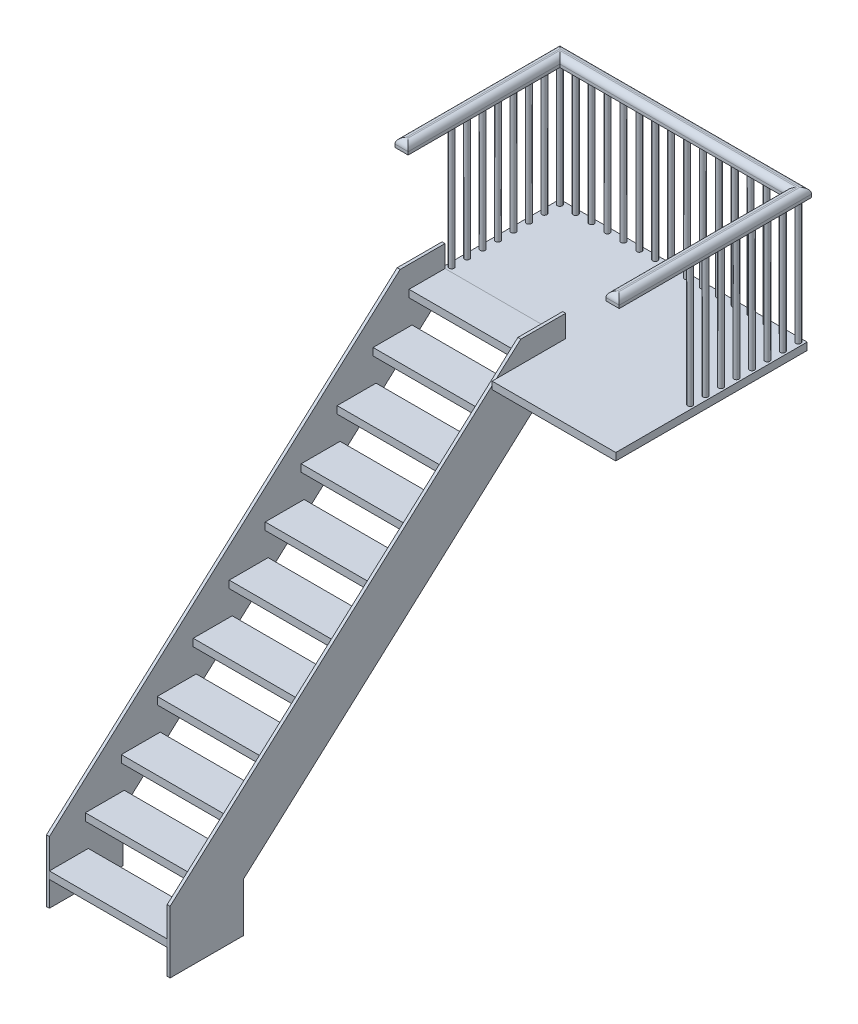
SolidWorks part; units mm, degrees
ref_plane "Front Plane" through (0, 0, 0) normal (0, 0, 1) x (1, 0, 0)
ref_plane "Top Plane" through (0, 0, 0) normal (0, 1, 0) x (1, 0, 0)
ref_plane "Right Plane" through (0, 0, 0) normal (1, 0, 0) x (0, 0, -1)
sketch "Sketch2" plane through (0, 0, 0) normal (1, 0, 0) x (0, 0, -1)
  line L0 (0, 0) -> (0, 8550) construction
  line L1 (0, 0) -> (-9495.737, 0) construction
  line L2 (0, 8550) -> (-9495.737, 0) construction
  line L3 (-9495.737, 170) -> (-9495.737, 220)
  line L4 (-9495.737, 220) -> (-9251.4022, 220)
  line L5 (-9251.4022, 390) -> (-9251.4022, 440)
  line L6 (-9251.4022, 440) -> (-9007.0675, 440)
  line L7 (-9007.0675, 640) -> (-9007.0675, 660)
  line L8 (-9007.0675, 660) -> (-8762.7327, 660)
  line L9 (-8762.7327, 860) -> (-8762.7327, 880)
  line L10 (-8762.7327, 880) -> (-8518.398, 880)
  line L11 (-8518.398, 1080) -> (-8518.398, 1100)
  line L12 (-8518.398, 1100) -> (-8274.0632, 1100)
  line L13 (-8274.0632, 1300) -> (-8274.0632, 1320)
  line L14 (-8274.0632, 1320) -> (-8029.7285, 1320)
  line L15 (-8029.7285, 1520) -> (-8029.7285, 1540)
  line L16 (-8029.7285, 1540) -> (-7785.3937, 1540)
  line L17 (-7785.3937, 1740) -> (-7785.3937, 1760)
  line L18 (-7785.3937, 1760) -> (-7541.059, 1760)
  line L19 (-7541.059, 1960) -> (-7541.059, 1980)
  line L20 (-7541.059, 1980) -> (-7296.7242, 1980)
  line L21 (-7296.7242, 2180) -> (-7296.7242, 2200)
  line L22 (-7296.7242, 2200) -> (-7052.3895, 2200)
  line L23 (-7052.3895, 2400) -> (-7052.3895, 2420)
  line L24 (-7052.3895, 2420) -> (-6808.0547, 2420)
  line L25 (-6808.0547, 2420) -> (-6808.0547, 2400)
  line L26 (-7032.3895, 2400) -> (-6788.0547, 2400) construction
  line L27 (-6808.0547, 2400) -> (-6830.267, 2400)
  line L28 (-9251.4022, 220) -> (-9231.4022, 220)
  line L31 (-6872.9593, 2410) -> (-5732.3596, 2410) construction
  line L32 (-9475.737, 0) -> (-9475.737, 18.0081) construction
  line L33 (-9475.737, 200) -> (-9231.4022, 200)
  line L34 (-9231.4022, 200) -> (-9231.4022, 220)
  line L35 (-9231.4022, 420) -> (-8987.0675, 420)
  line L36 (-8987.0675, 420) -> (-8987.0675, 440)
  line L37 (-8987.0675, 640) -> (-8742.7327, 640)
  line L38 (-8742.7327, 640) -> (-8742.7327, 660)
  line L39 (-8742.7327, 860) -> (-8498.398, 860)
  line L40 (-8498.398, 860) -> (-8498.398, 880)
  line L41 (-8498.398, 1080) -> (-8254.0632, 1080)
  line L42 (-8254.0632, 1080) -> (-8254.0632, 1100)
  line L43 (-8254.0632, 1300) -> (-8009.7285, 1300)
  line L44 (-8009.7285, 1300) -> (-8009.7285, 1320)
  line L45 (-8009.7285, 1520) -> (-7765.3937, 1520)
  line L46 (-7765.3937, 1520) -> (-7765.3937, 1540)
  line L47 (-7765.3937, 1740) -> (-7521.059, 1740)
  line L48 (-7521.059, 1740) -> (-7521.059, 1760)
  line L49 (-7521.059, 1960) -> (-7276.7242, 1960)
  line L50 (-7276.7242, 1960) -> (-7276.7242, 1980)
  line L51 (-7276.7242, 2180) -> (-7032.3895, 2180)
  line L52 (-7032.3895, 2180) -> (-7032.3895, 2200)
  line L53 (-7032.3895, 2400) -> (-6830.267, 2400)
  line L55 (-9007.0675, 440) -> (-8987.0675, 440)
  line L56 (-8762.7327, 660) -> (-8742.7327, 660)
  line L59 (-8518.398, 880) -> (-8498.398, 880)
  line L60 (-9495.737, 0) -> (-9475.737, 0) construction
  line L62 (-6299.3852, 3060) -> (-6075.0505, 3060) construction
  line L63 (-6319.3852, 3080) -> (-6075.0505, 3080) construction
  line L64 (-6299.3852, 2840) -> (-6299.3852, 3060) construction
  line L65 (-6319.3852, 2860) -> (-6319.3852, 3080) construction
  line L66 (-6563.72, 2860) -> (-6319.3852, 2860) construction
  line L67 (-6543.72, 2840) -> (-6299.3852, 2840) construction
  line L68 (-6543.72, 2620) -> (-6543.72, 2840) construction
  line L69 (-6563.72, 2640) -> (-6563.72, 2860) construction
  line L70 (-6808.0547, 2640) -> (-6563.72, 2640) construction
  line L71 (-6788.0547, 2620) -> (-6543.72, 2620) construction
  line L72 (-6788.0547, 2400) -> (-6788.0547, 2620) construction
  line L73 (-6808.0547, 2420) -> (-6808.0547, 2640) construction
  line L75 (-8274.0632, 1100) -> (-8254.0632, 1100)
  line L76 (-8029.7285, 1320) -> (-8009.7285, 1320)
  line L78 (-7785.3937, 1540) -> (-7765.3937, 1540)
  line L80 (-7541.059, 1760) -> (-7521.059, 1760)
  line L82 (-7296.7242, 1980) -> (-7276.7242, 1980)
  line L84 (-7052.3895, 2200) -> (-7032.3895, 2200)
  line L86 (-7032.3895, 2200) -> (-7032.3895, 2218.0081) construction
  line L87 (-7276.7242, 1980) -> (-7276.7242, 1998.0081) construction
  line L88 (-8009.7285, 1320) -> (-8009.7285, 1338.0081) construction
  line L89 (-8254.0632, 1100) -> (-8254.0632, 1118.0081) construction
  line L90 (-7032.3895, 2218.0081) -> (-7032.3895, 2400) construction
  line L91 (-7032.3895, 2180) -> (-7032.3895, 2400) construction
  line L92 (-7052.3895, 2200) -> (-7052.3895, 2400) construction
  line L93 (-7052.3895, 2200) -> (-7052.3895, 2420) construction
  line L94 (-8987.0675, 440) -> (-8987.0675, 458.0081) construction
  line L95 (-7276.7242, 1998.0081) -> (-7276.7242, 2180) construction
  line L96 (-7276.7242, 1960) -> (-7276.7242, 2180) construction
  line L97 (-7296.7242, 1980) -> (-7296.7242, 2180) construction
  line L98 (-7296.7242, 1980) -> (-7296.7242, 2200) construction
  line L99 (-7521.059, 1778.0081) -> (-7521.059, 1960) construction
  line L100 (-9231.4022, 220) -> (-9231.4022, 238.0081) construction
  line L101 (-7521.059, 1760) -> (-7521.059, 1778.0081) construction
  line L102 (-7521.059, 1740) -> (-7521.059, 1960) construction
  line L103 (-7541.059, 1760) -> (-7541.059, 1960) construction
  line L104 (-7541.059, 1760) -> (-7541.059, 1980) construction
  line L105 (-7765.3937, 1558.0081) -> (-7765.3937, 1740) construction
  line L106 (-7765.3937, 1520) -> (-7765.3937, 1740) construction
  line L107 (-7785.3937, 1540) -> (-7785.3937, 1740) construction
  line L108 (-7785.3937, 1540) -> (-7785.3937, 1760) construction
  line L109 (-8009.7285, 1338.0081) -> (-8009.7285, 1520) construction
  line L110 (-8009.7285, 1300) -> (-8009.7285, 1520) construction
  line L111 (-8029.7285, 1320) -> (-8029.7285, 1520) construction
  line L112 (-8029.7285, 1320) -> (-8029.7285, 1540) construction
  line L113 (-7765.3937, 1540) -> (-7765.3937, 1558.0081) construction
  line L114 (-9495.737, 170) -> (-9475.737, 170)
  line L115 (-8254.0632, 1118.0081) -> (-8254.0632, 1300) construction
  line L116 (-8254.0632, 1080) -> (-8254.0632, 1300) construction
  line L117 (-8274.0632, 1100) -> (-8274.0632, 1300) construction
  line L118 (-8274.0632, 1100) -> (-8274.0632, 1320) construction
  line L119 (-8498.398, 898.0081) -> (-8498.398, 1080) construction
  line L120 (-8498.398, 860) -> (-8498.398, 1080) construction
  line L121 (-8518.398, 880) -> (-8518.398, 1080) construction
  line L122 (-8518.398, 880) -> (-8518.398, 1100) construction
  line L123 (-8742.7327, 678.0081) -> (-8742.7327, 860) construction
  line L124 (-8742.7327, 640) -> (-8742.7327, 860) construction
  line L125 (-8762.7327, 660) -> (-8762.7327, 860) construction
  line L126 (-8762.7327, 660) -> (-8762.7327, 880) construction
  line L127 (-8498.398, 880) -> (-8498.398, 898.0081) construction
  line L128 (-8742.7327, 660) -> (-8742.7327, 678.0081) construction
  line L129 (-9475.737, 170) -> (-9475.737, 200)
  line L130 (-8987.0675, 458.0081) -> (-8987.0675, 640) construction
  line L131 (-8987.0675, 420) -> (-8987.0675, 640) construction
  line L132 (-9007.0675, 440) -> (-9007.0675, 640) construction
  line L133 (-9007.0675, 440) -> (-9007.0675, 660) construction
  line L134 (-9251.4022, 390) -> (-9231.4022, 390)
  line L135 (-9231.4022, 238.0081) -> (-9231.4022, 420) construction
  line L136 (-9231.4022, 200) -> (-9231.4022, 420) construction
  line L137 (-9251.4022, 220) -> (-9251.4022, 390) construction
  line L138 (-9251.4022, 220) -> (-9251.4022, 440) construction
  line L140 (-8987.0675, 640) -> (-8987.0675, 610)
  line L141 (-8987.0675, 610) -> (-9007.0675, 610)
  line L142 (-9475.737, 18.0081) -> (-9475.737, 170) construction
  line L143 (-9475.737, 0) -> (-9475.737, 200) construction
  line L144 (-9495.737, 0) -> (-9495.737, 170) construction
  line L145 (-9495.737, 0) -> (-9495.737, 220) construction
  line L146 (-9231.4022, 390) -> (-9231.4022, 420)
  line L147 (-8742.7327, 860) -> (-8742.7327, 830)
  line L148 (-8742.7327, 830) -> (-8762.7327, 830)
  line L149 (-8498.398, 1080) -> (-8498.398, 1050)
  line L150 (-8498.398, 1050) -> (-8518.398, 1050)
  line L151 (-8254.0632, 1300) -> (-8254.0632, 1270)
  line L152 (-8254.0632, 1270) -> (-8274.0632, 1270)
  line L153 (-8009.7285, 1520) -> (-8009.7285, 1490)
  line L154 (-8009.7285, 1490) -> (-8029.7285, 1490)
  line L155 (-7765.3937, 1740) -> (-7765.3937, 1710)
  line L156 (-7765.3937, 1710) -> (-7785.3937, 1710)
  line L157 (-7521.059, 1960) -> (-7521.059, 1930)
  line L158 (-7521.059, 1930) -> (-7541.059, 1930)
  line L159 (-7276.7242, 2180) -> (-7276.7242, 2150)
  line L160 (-7276.7242, 2150) -> (-7296.7242, 2150)
  line L161 (-7032.3895, 2400) -> (-7032.3895, 2370)
  line L162 (-7032.3895, 2370) -> (-7052.3895, 2370)
  line L163 (-9007.0675, 610) -> (-9007.0675, 640)
  line L164 (-8762.7327, 830) -> (-8762.7327, 860)
  line L165 (-8518.398, 1050) -> (-8518.398, 1080)
  line L166 (-8274.0632, 1270) -> (-8274.0632, 1300)
  line L167 (-8029.7285, 1490) -> (-8029.7285, 1520)
  line L168 (-7785.3937, 1710) -> (-7785.3937, 1740)
  line L169 (-7541.059, 1930) -> (-7541.059, 1960)
  line L170 (-7296.7242, 2150) -> (-7296.7242, 2180)
  line L171 (-7052.3895, 2400) -> (-7052.3895, 2370)
  dimension "D1" = 8550
  dimension "D2" = 42
  dimension "D3" = 12777.7745
  dimension "D4" = 9495.737
  dimension "D5" = 220
  dimension "D6" = 244.3348
  dimension "D7" = 2410
  dimension "D8" = 20
  dimension "D9" = 50
  dimension "D10" = 50
extrude "Stairs" add sketch "Sketch2" along normal blind 800 contours L3 L60 L32 L33 L34 L28 L4 | L56 L8 L7 L37 L38 | L59 L10 L9 L39 L40 | L75 L12 L11 L41 L42 | L76 L14 L13 L43 L44 | L78 L16 L15 L45 L46 | L80 L18 L17 L47 L48 | L84 L22 L21 L51 L52 | L53 L27 L25 L24 L23 | L6 L55 L36 L35 L146 L134 L5 | L20 L82 L50 L49 L157 L158 L169 L19 region at (0, 207.4519, 9376.0215) region at (0, 647.4519, 8887.352) region at (0, 867.4519, 8643.0172) region at (0, 1087.4519, 8398.6825) region at (0, 1307.4519, 8154.3477) region at (0, 1527.4519, 7910.013) region at (0, 1747.4519, 7665.6782) region at (0, 2187.4519, 7177.0087) region at (0, 2407.2661, 6942.4882)
sketch "Sketch3" plane through (800, 0, 0) normal (1, 0, 0) x (0, 0, -1)
  line L0 (-9495.737, 421.8449) -> (-7113.0101, 2567.2618)
  line L1 (-7113.0101, 2567.2618) -> (-6808.0547, 2567.2618)
  line L2 (-6808.0547, 2567.2618) -> (-6808.0547, 2303.5918)
  line L3 (-6808.0547, 2303.5918) -> (-8995.737, 333.7938)
  line L4 (-9495.737, 421.8449) -> (-9495.737, 0)
  line L5 (-9495.737, 0) -> (-9366.4526, 0)
  line L6 (-7052.3895, 2420) -> (-9495.737, 220) construction
  line L7 (-6808.0547, 2420) -> (-6808.0547, 2567.2618) construction
  line L9 (-8995.737, 333.7938) -> (-8995.737, 0)
  line L10 (-8995.737, 0) -> (-9366.4526, 0)
  line L11 (-8995.737, 333.7938) -> (-9366.4526, 0) construction
  dimension "D1" = 150
  dimension "D2" = 400
  dimension "D3" = 500
extrude "Right Stringer" add sketch "Sketch3" along normal blind 20
sketch "Sketch4" plane through (0, 0, 0) normal (-1, 0, 0) x (0, 0, 1)
  line L0 (8995.737, 333.7938) -> (6808.0547, 2303.5918) construction
  line L5 (7113.0101, 2567.2618) -> (9495.737, 421.8449) construction
  line L6 (6808.0547, 2567.2618) -> (7113.0101, 2567.2618) construction
  line L9 (8995.737, 333.7938) -> (6808.0547, 2303.5918)
  line L14 (7113.0101, 2567.2618) -> (9495.737, 421.8449)
  line L15 (6808.0547, 2567.2618) -> (7113.0101, 2567.2618)
  line L16 (6808.0547, 2567.2618) -> (6808.0547, 2303.5918)
  line L18 (9495.737, 333.7938) -> (9495.737, 421.8449)
  line L20 (8995.737, 333.7938) -> (8995.737, 0)
  line L21 (8995.737, 0) -> (9495.737, 0)
  line L22 (9495.737, 0) -> (9495.737, 333.7938)
extrude "Left Stringer" add sketch "Sketch4" along normal blind 20
sketch "Sketch5" plane through (0, 0, 6808.0547) normal (0, 0, -1) x (-1, 0, 0)
  line L0 (-820, 2303.5918) -> (-820, 2567.2618) construction
  line L1 (-820, 2417.6283) -> (20, 2417.6283)
  line L2 (-820, 2417.6283) -> (-820, 2367.6283)
  line L3 (-820, 2367.6283) -> (20, 2367.6283)
  line L4 (20, 2417.6283) -> (20, 2367.6283)
  line L5 (20, 2567.2618) -> (20, 2303.5918) construction
  point P4 (0, 0)
  point P5 (-820, 2419.0728)
  point P9 (20, 2417.6283)
  dimension "D1" = 50
extrude "Boss-Extrude6" add sketch "Sketch5" along normal blind 800
sketch "Sketch6" plane through (820, 0, 0) normal (1, 0, 0) x (0, 0, -1)
  line L1 (-6008.0547, 2417.6283) -> (-6808.0547, 2417.6283)
  line L2 (-6008.0547, 2417.6283) -> (-6008.0547, 2367.6283)
  line L3 (-6008.0547, 2367.6283) -> (-6808.0547, 2367.6283)
  line L4 (-6808.0547, 2417.6283) -> (-6808.0547, 2367.6283)
extrude "Boss-Extrude7" add sketch "Sketch6" along normal blind 840
sketch "Sketch7" plane through (0, 0, 6808.0547) normal (0, 0, 1) x (1, 0, 0)
  line L4 (820, 2417.6283) -> (820, 2367.6283)
  line L5 (820, 2367.6283) -> (1660, 2367.6283)
  line L6 (1660, 2367.6283) -> (1660, 2417.6283)
  line L7 (1660, 2417.6283) -> (820, 2417.6283)
  line L8 (820, 2417.6283) -> (820, 2367.6283)
  line L9 (820, 2367.6283) -> (1660, 2367.6283)
  line L10 (1660, 2367.6283) -> (1660, 2417.6283)
  line L11 (1660, 2417.6283) -> (820, 2417.6283)
  dimension "D1" = 0
extrude "Boss-Extrude8" add sketch "Sketch7" along normal blind 500
sketch "Sketch8" plane through (0, 2417.6283, 0) normal (0, 1, 0) x (1, 0, 0)
  line L0 (10, -6008.0547) -> (10, -6808.0547) construction
  line L1 (-20, -6008.0547) -> (1660, -6008.0547) construction
  line L2 (800, -6808.0547) -> (0, -6808.0547) construction
  line L3 (-20, -6038.0547) -> (1660, -6038.0547) construction
  line L4 (-20, -6008.0547) -> (-20, -6808.0547) construction
  line L5 (1660, -6008.0547) -> (1660, -7308.0547) construction
  line L6 (1630, -6008.0547) -> (1630, -7308.0547) construction
  line L7 (1660, -7308.0547) -> (820, -7308.0547) construction
  circle A0 centre (10, -6038.0547) radius 17
  circle A16 centre (10, -6143.0547) radius 17
  circle A17 centre (10, -6248.0547) radius 17
  circle A18 centre (10, -6353.0547) radius 17
  circle A19 centre (10, -6458.0547) radius 17
  circle A20 centre (10, -6563.0547) radius 17
  circle A21 centre (10, -6668.0547) radius 17
  circle A22 centre (10, -6773.0547) radius 17
  circle A23 centre (10, -6143.0547) radius 17
  circle A25 centre (10, -6248.0547) radius 17
  circle A27 centre (10, -6353.0547) radius 17
  circle A29 centre (10, -6458.0547) radius 17
  circle A31 centre (10, -6563.0547) radius 17
  circle A33 centre (10, -6668.0547) radius 17
  circle A35 centre (10, -6773.0547) radius 17
  circle A37 centre (118, -6038.0547) radius 17
  circle A38 centre (226, -6038.0547) radius 17
  circle A39 centre (334, -6038.0547) radius 17
  circle A40 centre (442, -6038.0547) radius 17
  circle A41 centre (550, -6038.0547) radius 17
  circle A42 centre (658, -6038.0547) radius 17
  circle A43 centre (766, -6038.0547) radius 17
  circle A44 centre (874, -6038.0547) radius 17
  circle A45 centre (982, -6038.0547) radius 17
  circle A46 centre (1090, -6038.0547) radius 17
  circle A47 centre (1198, -6038.0547) radius 17
  circle A48 centre (1306, -6038.0547) radius 17
  circle A49 centre (1414, -6038.0547) radius 17
  circle A50 centre (1522, -6038.0547) radius 17
  circle A51 centre (1630, -6038.0547) radius 17
  circle A52 centre (10, -6143.0547) radius 17
  circle A53 centre (1630, -6143.0547) radius 17
  circle A54 centre (10, -6248.0547) radius 17
  circle A55 centre (1630, -6248.0547) radius 17
  circle A56 centre (10, -6353.0547) radius 17
  circle A57 centre (1630, -6353.0547) radius 17
  circle A58 centre (10, -6458.0547) radius 17
  circle A59 centre (1630, -6458.0547) radius 17
  circle A60 centre (10, -6563.0547) radius 17
  circle A61 centre (1630, -6563.0547) radius 17
  circle A62 centre (10, -6668.0547) radius 17
  circle A63 centre (1630, -6668.0547) radius 17
  circle A64 centre (10, -6773.0547) radius 17
  circle A65 centre (1630, -6773.0547) radius 17
  dimension "D1" = 1620
  dimension "D2" = 16
  dimension "D3" = 8
  dimension "D6" = 8
  dimension "D7" = 8
extrude "Boss-Extrude9" add sketch "Sketch8" along normal blind 850 contours A22 | A21 | A20 | A16 | A17 | A18 | A19 | A53 | A54 | A55 | A56 | A57 | A58 | A37 | A38 | A39 | A40 | A41 | A42 | A43 | A44 | A45 | A46 | A47 | A48 | A49 | A50 | A51 | A59 | A61 | A63 | A65 | A0 region at (10, 2417.6283, 6143.0547) region at (10, 2417.6283, 6248.0547) region at (10, 2417.6283, 6353.0547) region at (10, 2417.6283, 6458.0547) region at (10, 2417.6283, 6563.0547) region at (10, 2417.6283, 6668.0547) region at (10, 2417.6283, 6773.0547) region at (118, 2417.6283, 6038.0547) region at (226, 2417.6283, 6038.0547) region at (334, 2417.6283, 6038.0547) region at (442, 2417.6283, 6038.0547) region at (550, 2417.6283, 6038.0547) region at (658, 2417.6283, 6038.0547) region at (766, 2417.6283, 6038.0547) region at (874, 2417.6283, 6038.0547) region at (982, 2417.6283, 6038.0547) region at (1090, 2417.6283, 6038.0547) region at (1198, 2417.6283, 6038.0547) region at (1306, 2417.6283, 6038.0547) region at (1414, 2417.6283, 6038.0547) region at (1522, 2417.6283, 6038.0547) region at (1630, 2417.6283, 6038.0547) region at (1630, 2417.6283, 6143.0547) region at (1630, 2417.6283, 6248.0547) region at (1630, 2417.6283, 6353.0547) region at (1630, 2417.6283, 6458.0547) region at (1630, 2417.6283, 6563.0547) region at (1630, 2417.6283, 6668.0547) region at (1630, 2417.6283, 6773.0547)
sketch "Sketch9" plane through (0, 3267.6283, 0) normal (0, 1, 0) x (1, 0, 0)
  line L0 (10, -6038.0547) -> (10, -6773.0547) construction
  line L1 (-35, -5993.0547) -> (55, -5993.0547)
  line L2 (-35, -5993.0547) -> (-35, -7113.3678)
  line L3 (-35, -7113.3678) -> (55, -7113.3678)
  line L4 (55, -6083.0547) -> (55, -7113.3678)
  line L5 (55, -5993.0547) -> (1675, -5993.0547)
  line L7 (55, -6083.0547) -> (1585, -6083.0547)
  line L8 (1675, -5993.0547) -> (1675, -6083.0547)
  line L10 (1675, -6083.0547) -> (1675, -7299.5141)
  line L11 (1675, -7299.5141) -> (1585, -7299.5141)
  line L12 (1585, -6083.0547) -> (1585, -7299.5141)
  line L13 (10, -6038.0547) -> (1630, -6038.0547) construction
  line L14 (1630, -6038.0547) -> (1630, -6773.0547) construction
  dimension "D1" = 90
  dimension "D2" = 45
  dimension "D3" = 45
  dimension "D4" = 90
  dimension "D5" = 45
  dimension "D6" = 90
extrude "Boss-Extrude11" add sketch "Sketch9" along normal blind 60
fillet "Fillet1" radius 40 8 edges at (820, 3327.6283, 5993.0547) (1675, 3327.6283, 6646.2844) (1630, 3327.6283, 7299.5141) (1585, 3327.6283, 6691.2844) (820, 3327.6283, 6083.0547) (55, 3327.6283, 6598.2113) (10, 3327.6283, 7113.3678) (-35, 3327.6283, 6553.2113)
